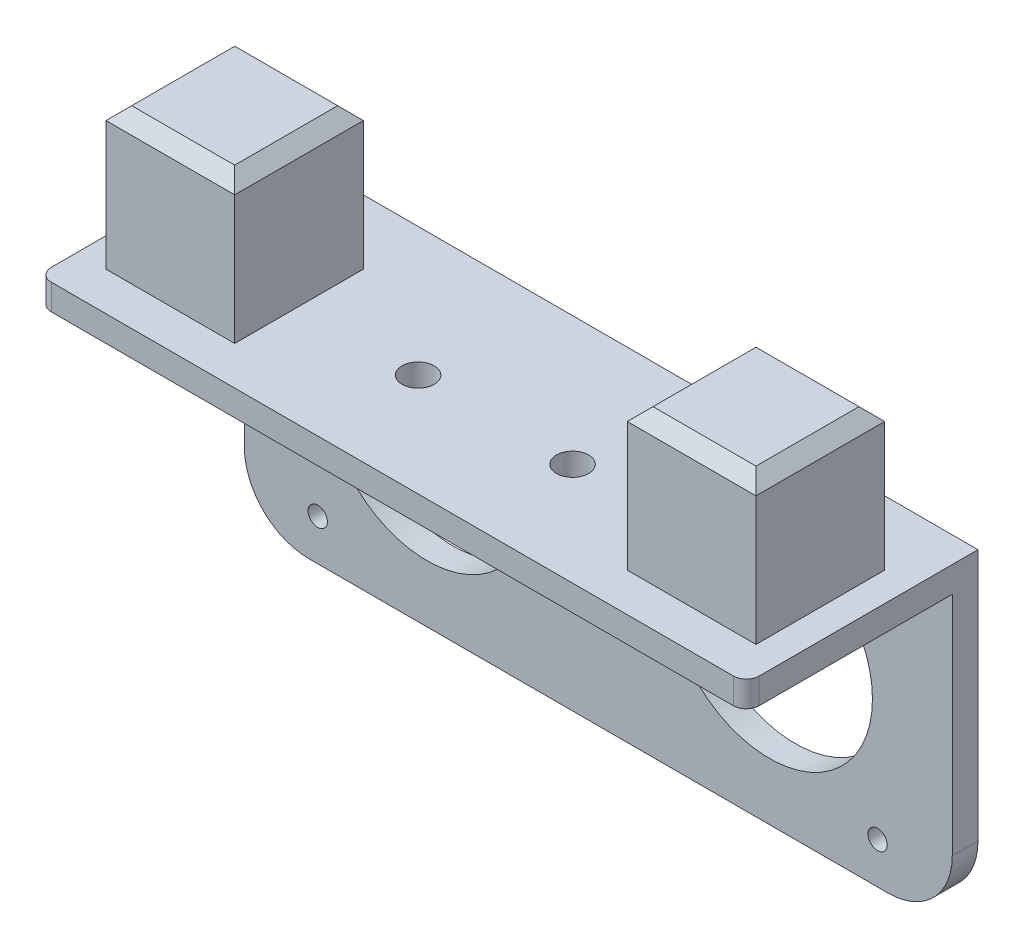
SolidWorks part; units mm, degrees
other "Markup1"
sketch "Sketch7" plane through (-20.0719, -0.3318, 12) normal (-0.8831, -0.2604, 0.3903) x (-0.3657, -0.1393, -0.9203)
other "Markup2"
sketch "Sketch23" plane through (-28.5719, 1.0682, 18) normal (-0.0368, -0.1105, 0.9932) x (-0.9991, 0.0251, -0.0342)
other "Markup3"
sketch "Sketch24" plane through (-28.5719, 1.0682, 18) normal (-0.0368, -0.1105, 0.9932) x (-0.9991, 0.0251, -0.0342)
ref_plane "Front Plane" through (0, 0, 0) normal (0, 0, 1) x (1, 0, 0)
ref_plane "Top Plane" through (0, 0, 0) normal (0, 1, 0) x (1, 0, 0)
ref_plane "Right Plane" through (0, 0, 0) normal (1, 0, 0) x (0, 0, -1)
sketch "Sketch1" plane through (0, 0, 0) normal (0, 0, 1) x (1, 0, 0)
  line L1 (-28.5719, 23.6682) -> (26.4281, 23.6682)
  line L2 (-28.5719, 23.6682) -> (-28.5719, 1.0682)
  line L3 (-28.5719, 1.0682) -> (26.4281, 1.0682)
  line L4 (26.4281, 23.6682) -> (26.4281, 1.0682)
  dimension "D1" = 55
  dimension "D2" = 22.6
extrude "Boss-Extrude1" add sketch "Sketch1" along normal blind 2 contours L1 L4 L3 L2
sketch "Sketch2" plane through (0, 0, 2) normal (0, 0, 1) x (1, 0, 0)
  line L1 (-28.5719, 23.6682) -> (26.4281, 23.6682) construction
  line L4 (-28.5719, 23.6682) -> (-28.5719, 1.0682) construction
  circle A0 centre (-14.3719, 13.5182) radius 8
  circle A1 centre (12.2281, 13.5182) radius 8
  dimension "D5" = 16
  dimension "D6" = 16
  dimension "D1" = 26.6
  dimension "D2" = 10.15
  dimension "D3" = 14.2
  dimension "D4" = 10.15
extrude "Cut-Extrude2" cut sketch "Sketch2" against normal blind 2 contours A0
extrude "Cut-Extrude3" cut sketch "Sketch2<4>" against normal blind 2
sketch "Sketch2<4>" plane through (0, 0, 2) normal (0, 0, 1) x (1, 0, 0) same geometry as "Sketch2"
sketch "Sketch5" plane through (0, 0, 2) normal (0, 0, 1) x (1, 0, 0)
  line L0 (-28.5719, 23.6682) -> (26.4281, 23.6682) construction
  line L1 (-6.1719, 23.6682) -> (3.8281, 23.6682)
  line L2 (-6.1719, 23.6682) -> (-6.1719, 19.0682)
  line L3 (-6.1719, 19.0682) -> (3.8281, 19.0682)
  line L4 (3.8281, 23.6682) -> (3.8281, 19.0682)
  line L5 (-28.5719, 23.6682) -> (-28.5719, 1.0682) construction
  dimension "D1" = 4.6
  dimension "D2" = 10
  dimension "D3" = 22.4
extrude "Cut-Extrude4" cut sketch "Sketch5" against normal blind 2 contours L3 L4 L1 L2
sketch "Sketch6" plane through (0, 0, 0) normal (0, 0, -1) x (-1, 0, 0)
  line L1 (28.5719, 25.6682) -> (-26.4281, 25.6682)
  line L2 (28.5719, 25.6682) -> (28.5719, 23.6682)
  line L3 (28.5719, 23.6682) -> (-26.4281, 23.6682)
  line L4 (-26.4281, 25.6682) -> (-26.4281, 23.6682)
  dimension "D1" = 55
  dimension "D2" = 2
extrude "Boss-Extrude2" add sketch "Sketch6" against normal blind 18 contours L1 L4 L3 L2
sketch "Sketch9" plane through (0, 23.6682, 0) normal (0, -1, 0) x (-1, 0, 0)
  line L1 (28.5719, -18) -> (28.5719, -2) construction
  line L4 (-26.4281, -18) -> (-26.4281, -2) construction
  line L5 (26.3219, -15) -> (16.3219, -15)
  line L6 (26.3219, -15) -> (26.3219, -5)
  line L7 (26.3219, -5) -> (16.3219, -5)
  line L8 (16.3219, -15) -> (16.3219, -5)
  line L9 (-14.1781, -15) -> (-24.1781, -15)
  line L10 (-14.1781, -15) -> (-14.1781, -5)
  line L11 (-14.1781, -5) -> (-24.1781, -5)
  line L12 (-24.1781, -15) -> (-24.1781, -5)
  dimension "D4" = 10
  dimension "D5" = 10
  dimension "D6" = 10
  dimension "D7" = 10
  dimension "D8" = 2.25
  dimension "D9" = 2.25
extrude "Boss-Extrude4" add sketch "Sketch9" against normal blind 13
sketch "Sketch18" plane through (0, 23.6682, 0) normal (0, -1, 0) x (-1, 0, 0)
  line L0 (7.0719, -10) -> (-4.9281, -10)
  line L1 (-26.4281, -18) -> (-26.4281, -2) construction
  point P3 (1.0719, -10)
  dimension "D1" = 12
  dimension "D2" = 21.5
hole_wizard "M3x0.5 Tapped Hole1" positions "Sketch19" profile "Sketch20" tap size "M3x0.5" standard "ANSI Metric" end condition through all
sketch "Sketch19" plane through (0, 23.6682, 0) normal (0, -1, 0) x (-1, 0, 0)
  point P0 (-4.9281, -10)
sketch "Sketch20" plane through (4.9281, 23.6682, 10) normal (1, 0, 0) x (0, 0, -1)
  line L0 (0, 0) -> (0, 13)
  line L1 (0, 13) -> (1.25, 13)
  line L2 (1.25, 13) -> (1.25, 0)
  line L5 (1.25, 0) -> (0, 0)
  line L11 (0, -6.35) -> (0, 107.95) construction
  dimension "Thru Tap Drill Dia." = 2.5
  dimension "Thru Tap Drill Depth" = 13
cosmetic thread "Hole Thread1" parameters "D2"=3
hole_wizard "M3x0.5 Tapped Hole2" positions "Sketch21" profile "Sketch22" tap size "M3x0.5" standard "ANSI Metric" end condition through all
sketch "Sketch21" plane through (0, 23.6682, 0) normal (0, -1, 0) x (-1, 0, 0)
  point P0 (7.0719, -10)
sketch "Sketch22" plane through (-7.0719, 23.6682, 10) normal (1, 0, 0) x (0, 0, -1)
  line L0 (0, 0) -> (0, 13)
  line L1 (0, 13) -> (1.25, 13)
  line L2 (1.25, 13) -> (1.25, 0)
  line L5 (1.25, 0) -> (0, 0)
  line L11 (0, -6.35) -> (0, 107.95) construction
  dimension "Thru Tap Drill Dia." = 2.5
  dimension "Thru Tap Drill Depth" = 13
cosmetic thread "Hole Thread2" parameters "D2"=3
fillet "Fillet1" radius 5 1 edges at (-28.5719, 1.0682, 1) type face fillet first side face at (-1.0719, 1.0682, 1) second side face at (-28.5719, 16.8015, 6.6667)
fillet "Fillet2" radius 5 1 edges at (26.4281, 1.0682, 1) type face fillet first side face at (1.4281, 1.0682, 1) second side face at (26.4281, 16.8015, 6.6667)
fillet "Fillet4" radius 1.8 1 edges at (3.8281, 19.0682, 1)
fillet "Fillet5" radius 1.8 1 edges at (-6.1719, 19.0682, 1)
chamfer "Chamfer2" distance 1 angle 45 8 edges at (19.1781, 36.6682, 15) (14.1781, 36.6682, 10) (19.1781, 36.6682, 5) (24.1781, 36.6682, 10) (-21.3219, 36.6682, 15) (-26.3219, 36.6682, 10) (-21.3219, 36.6682, 5) (-16.3219, 36.6682, 10)
fillet "Fillet10" radius 1 2 edges at (26.4281, 24.6682, 18) (-28.5719, 24.6682, 18)
sketch "Sketch25" plane through (0, 0, 2) normal (0, 0, 1) x (1, 0, 0)
  line L0 (26.4281, 23.6682) -> (26.4281, 6.0682) construction
  circle A0 centre (20.6281, 4.2682) radius 0.75
  circle A1 centre (20.6281, 22.7682) radius 0.75
  circle A3 centre (-22.8719, 4.2682) radius 0.75
  circle A4 centre (-22.8719, 22.7682) radius 0.75
  dimension "D1" = 1.5
  dimension "D7" = 1.5
  dimension "D5" = 5.8
  dimension "D6" = 18.5
  dimension "D12" = 43.5
extrude "Cut-Extrude5" cut sketch "Sketch25" against normal blind 10
